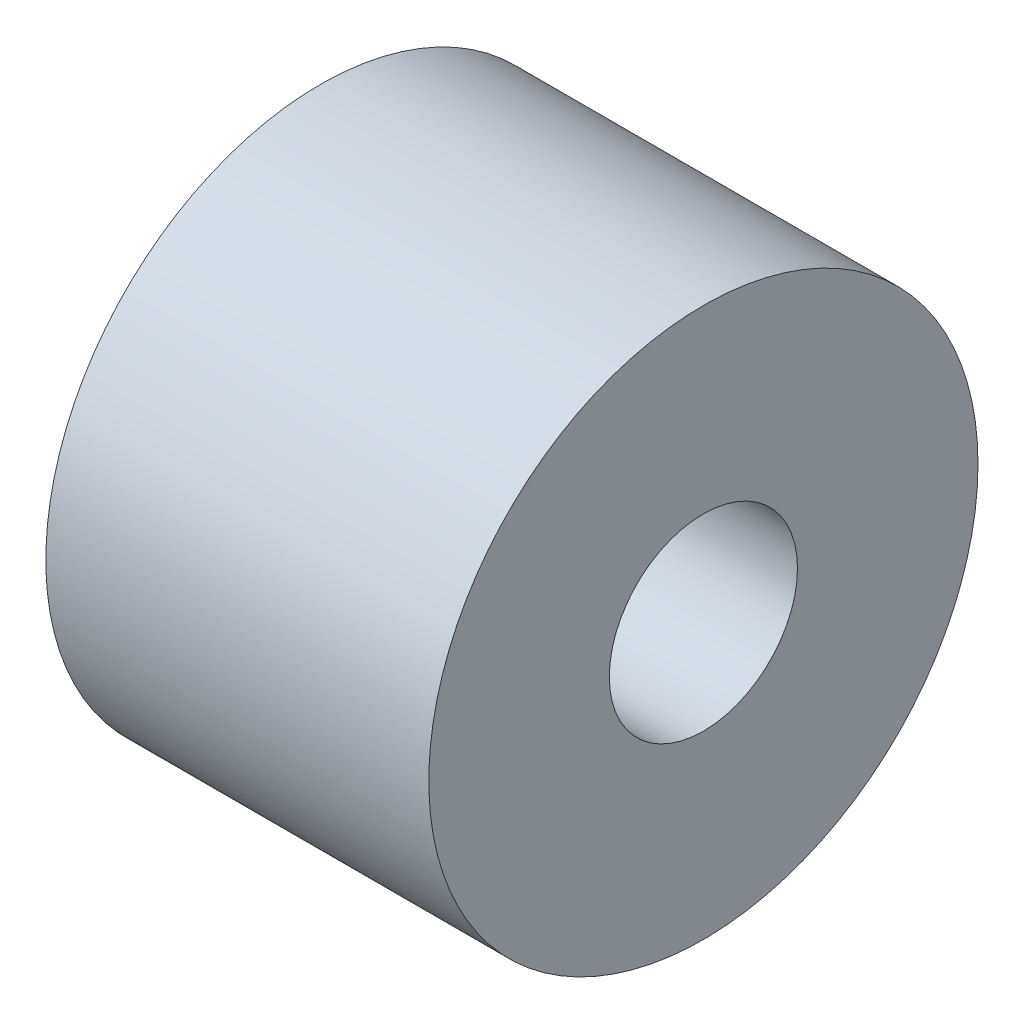
SolidWorks part; units mm, degrees
material "DELRIN (WHITE)"
ref_plane "Front" through (0, 0, 0) normal (0, 0, 1) x (1, 0, 0)
ref_plane "Top" through (0, 0, 0) normal (0, 1, 0) x (1, 0, 0)
ref_plane "Right" through (0, 0, 0) normal (1, 0, 0) x (0, 0, -1)
ref_axis "Axis1" through (0, 50, 0) along (0, -1, 0)
sketch "Sketch1" plane through (0, 0, 0) normal (1, 0, 0) x (0, 0, -1)
  circle A0 centre (0, 0) radius 9.525
  dimension "D1" = 19.05
extrude "Extrude1" add sketch "Sketch1" along normal mid plane 13.2842
sketch "Sketch2" plane through (6.6421, 0, 0) normal (1, 0, 0) x (0, 0, -1)
  circle A0 centre (0, 0) radius 3.2639
  dimension "D1" = 6.5278
extrude "Extrude2" cut sketch "Sketch2" against normal through all
